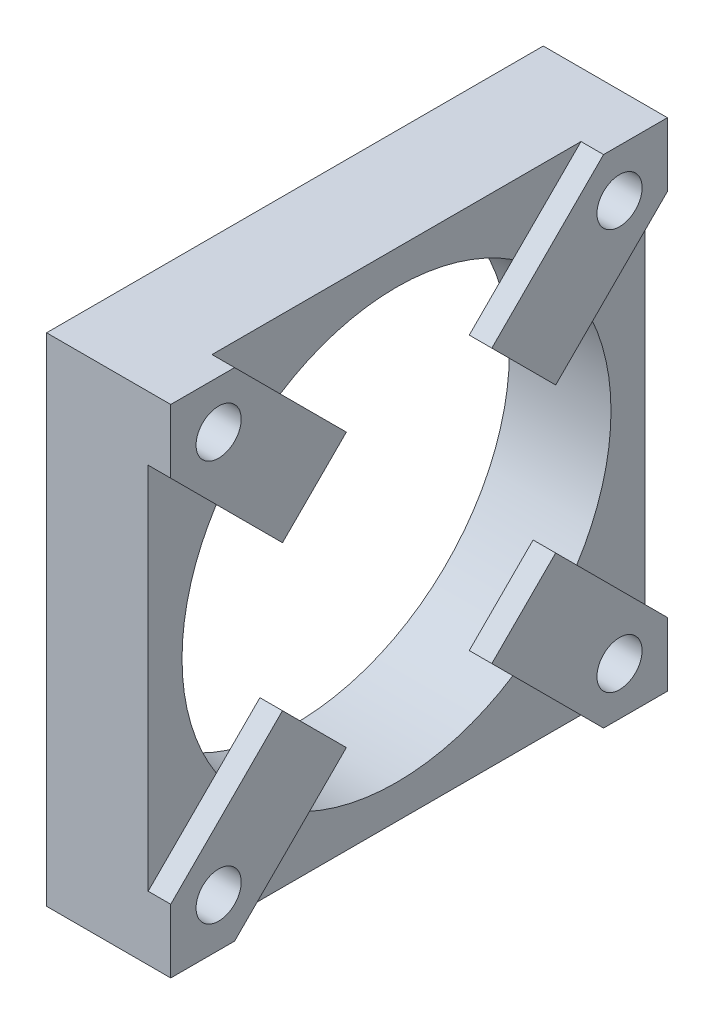
SolidWorks part; units mm, degrees
ref_plane "Front Plane" through (0, 0, 0) normal (0, 0, 1) x (1, 0, 0)
ref_plane "Top Plane" through (0, 0, 0) normal (0, 1, 0) x (1, 0, 0)
ref_plane "Right Plane" through (0, 0, 0) normal (1, 0, 0) x (0, 0, -1)
sketch "Sketch1" plane through (0, 0, 0) normal (1, 0, 0) x (0, 0, -1)
  line L1 (-27.94, 27.94) -> (27.94, 27.94)
  line L2 (-27.94, 27.94) -> (-27.94, -27.94)
  line L3 (-27.94, -27.94) -> (27.94, -27.94)
  line L4 (27.94, 27.94) -> (27.94, -27.94)
  line L5 (-27.94, 27.94) -> (27.94, -27.94) construction
  line L6 (-27.94, -27.94) -> (27.94, 27.94) construction
  circle A0 centre (0, 0) radius 24.13
  point P0 (0, 0)
  dimension "D1" = 48.26
  dimension "D2" = 55.88
  dimension "D3" = 55.88
extrude "Boss-Extrude1" add sketch "Sketch1" along normal blind 11.43
sketch "Sketch2" plane through (11.43, 0, 0) normal (1, 0, 0) x (0, 0, -1)
  line L0 (-27.94, 20.7558) -> (-27.94, 27.94)
  line L2 (-27.94, 27.94) -> (-20.7558, 27.94)
  line L3 (27.94, 27.94) -> (-27.94, 27.94) construction
  line L4 (-27.94, 27.94) -> (0, 0) construction
  line L5 (-27.94, 20.7558) -> (-15.3676, 8.1834)
  line L6 (-20.7558, 27.94) -> (-8.1834, 15.3676)
  line L7 (-15.3676, 8.1834) -> (-8.1834, 15.3676)
  line L8 (-24.3479, 31.5321) -> (3.5921, 3.5921) construction
  line L9 (-31.5321, 24.3479) -> (-3.5921, -3.5921) construction
  dimension "D3" = 22.86
  dimension "D1" = 5.08
  dimension "D2" = 5.08
extrude "Boss-Extrude2" add sketch "Sketch2" along normal blind 2.54
pattern_circular "CirPattern1" count 4 over 360 about axis through (11.43, 0, 0) along (1, 0, 0) of "Boss-Extrude2"
sketch "Sketch5" plane through (0, 0, 0) normal (1, 0, 0) x (0, 0, -1)
  line L0 (-27.94, -27.94) -> (0, 0) construction
  circle A0 centre (-22.5518, -22.5518) radius 2.54
  circle A1 centre (-22.5518, 22.5518) radius 2.54
  circle A2 centre (22.5518, 22.5518) radius 2.54
  circle A3 centre (22.5518, -22.5518) radius 2.54
  point P15 (0, 0)
  dimension "D1" = 5.08
  dimension "D2" = 7.62
  dimension "D3" = 4
extrude "Cut-Extrude2" cut sketch "Sketch5" against normal through all and the other way through all
